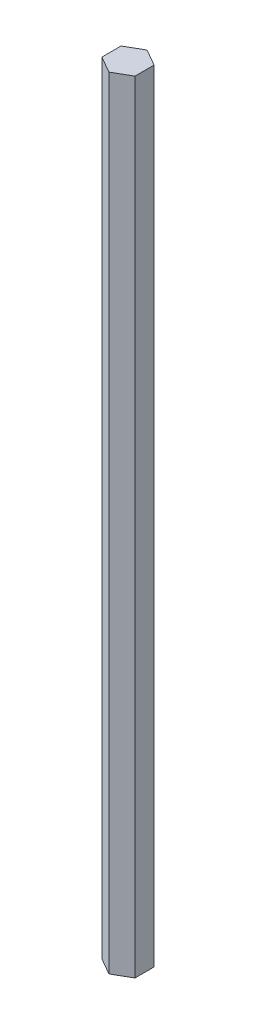
SolidWorks part; units mm, degrees
ref_plane "Front Plane" through (0, 0, 0) normal (0, 0, 1) x (1, 0, 0)
ref_plane "Top Plane" through (0, 0, 0) normal (0, 1, 0) x (1, 0, 0)
ref_plane "Right Plane" through (0, 0, 0) normal (1, 0, 0) x (0, 0, -1)
sketch "Sketch1" plane through (0, 0, 0) normal (0, 1, 0) x (1, 0, 0)
  line L1 (6.3495, -3.6671) -> (6.3505, 3.6653)
  line L2 (6.3505, 3.6653) -> (0.0011, 7.3323)
  line L3 (0.0011, 7.3323) -> (-6.3495, 3.6671)
  line L4 (-6.3495, 3.6671) -> (-6.3505, -3.6653)
  line L5 (-6.3505, -3.6653) -> (-0.0011, -7.3323)
  line L6 (-0.0011, -7.3323) -> (6.3495, -3.6671)
  circle A1 centre (0, 0) radius 6.35 construction
extrude "Boss-Extrude1" add sketch "Sketch1" along normal mid plane 300
ref_axis "Axis1" through (0, 176.9166, 0) along (0, -1, 0)
